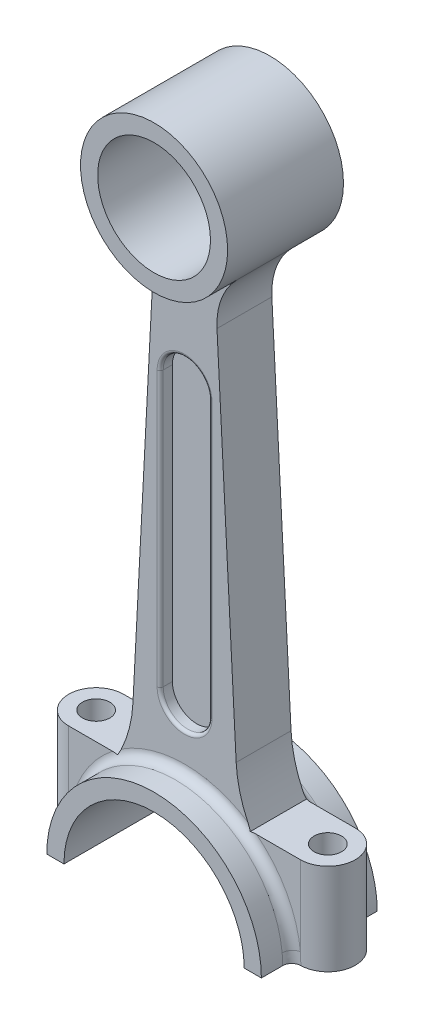
SolidWorks part; units mm, degrees
ref_plane "Front Plane" through (0, 0, 0) normal (0, 0, 1) x (1, 0, 0)
ref_plane "Top Plane" through (0, 0, 0) normal (0, 1, 0) x (1, 0, 0)
ref_plane "Right Plane" through (0, 0, 0) normal (1, 0, 0) x (0, 0, -1)
sketch "Sketch1" plane through (0, 0, 0) normal (0, 0, 1) x (1, 0, 0)
  line L0 (0, 0) -> (0, -201.2) construction
  line L1 (-10, -21.9525) -> (-17.8029, -170.8403)
  line L2 (10, -21.9525) -> (17.8029, -170.8403)
  line L3 (-35.1946, -201.2) -> (-29.5574, -201.2)
  line L4 (29.5574, -201.2) -> (35.1946, -201.2)
  circle A0 centre (0, 0) radius 24.1229
  circle A1 centre (0, 0) radius 18.5007
  arc A2 (35.1946, -201.2) -> (-35.1946, -201.2) centre (0, -201.2) ccw
  arc A3 (29.5574, -201.2) -> (-29.5574, -201.2) centre (0, -201.2) ccw
  dimension "D1" = 201.2
  dimension "D2" = 20
  dimension "D3" = 6
extrude "Boss-Extrude1" add sketch "Sketch1" along normal mid plane 38 contours A2 A3 | A1 A0 | L4 A2 L3 A3 region at (-12.6824, 19.7134, 0) region at (0, -166.7924, 0)
extrude "Boss-Extrude2" add sketch "Sketch1<3>" along normal mid plane 18 contours A0 L0 A2 L2 | L0 A0 L1 A2 region at (7.1692, -102.039, 0) region at (-7.1692, -102.039, 0)
sketch "Sketch1<3>" plane through (0, 0, 0) normal (0, 0, 1) x (1, 0, 0) same geometry as "Sketch1"
sketch "Sketch2" plane through (0, 0, 9) normal (0, 0, 1) x (1, 0, 0)
  line L0 (0, 0) -> (0, -201.2) construction
  line L1 (0, -145.6) -> (0, -55.6) construction
  line L2 (-8, -145.6) -> (-8, -55.6)
  line L3 (8, -145.6) -> (8, -55.6)
  arc A0 (-8, -145.6) -> (8, -145.6) centre (0, -145.6) ccw
  arc A1 (8, -55.6) -> (-8, -55.6) centre (0, -55.6) ccw
  point P6 (0, -100.6)
  dimension "D2" = 8
  dimension "D1" = 90
extrude "Cut-Extrude1" cut sketch "Sketch2" against normal blind 4 and the other way through all
mirror "Mirror1" about plane through (0, 0, 0) normal (0, 0, 1) of "Cut-Extrude1"
fillet "Fillet1" radius 1 8 edges at (0, -47.6, -5) (8, -100.6, -5) (0, -153.6, -5) (8, -100.6, 9) (0, -47.6, 9) (0, -153.6, 9) (-8, -100.6, 9) (-8, -100.6, -5)
fillet "Fillet2" radius 40 2 edges at (17.8029, -170.8403, 0) (-17.8029, -170.8403, 0)
fillet "Fillet3" radius 22.5 2 edges at (10, -21.9525, 0) (-10, -21.9525, 0)
ref_plane "Plane1" through (0, -171.2, 0) normal (0, -1, 0) x (-1, 0, 0)
sketch "Sketch3" plane through (0, -171.2, 0) normal (0, -1, 0) x (-1, 0, 0)
  line L0 (38, 0) -> (-38, 0) construction
  line L1 (38, -9) -> (-38, -9)
  line L2 (38, 9) -> (-38, 9)
  arc A0 (38, -9) -> (38, 9) centre (38, 0) ccw
  arc A1 (-38, 9) -> (-38, -9) centre (-38, 0) ccw
  point P2 (0, 0)
  dimension "D2" = 9
  dimension "D1" = 76
extrude "Boss-Extrude3" add sketch "Sketch3" along normal up to surface (30 mm away) up to face at (-32.376, -201.2, 0)
sketch "Sketch4" plane through (0, 0, 9) normal (0, 0, 1) x (1, 0, 0)
  line L1 (-29.5574, -201.2) -> (29.5574, -201.2)
  line L2 (-29.5574, -201.2) -> (29.5574, -201.2)
  arc A1 (29.5574, -201.2) -> (-29.5574, -201.2) centre (0, -201.2) ccw
  arc A2 (29.5574, -201.2) -> (-29.5574, -201.2) centre (0, -201.2) ccw
  dimension "D1" = 0
extrude "Cut-Extrude2" cut sketch "Sketch4" against normal through all
sketch "Sketch5" plane through (0, -171.2, 0) normal (0, 1, 0) x (1, 0, 0)
  circle A0 centre (-38, 0) radius 4.5
  circle A1 centre (38, 0) radius 4.5
extrude "Cut-Extrude3" cut sketch "Sketch5" against normal through all
fillet "Fillet4" radius 3 2 edges at (0, -166.0054, -9) (0, -166.0054, 9)
